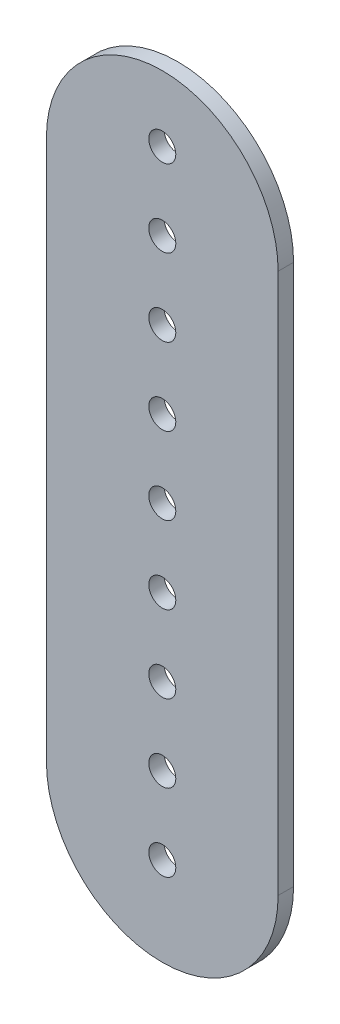
SolidWorks part; units mm, degrees
ref_plane "Front Plane" through (0, 0, 0) normal (0, 0, 1) x (1, 0, 0)
ref_plane "Top Plane" through (0, 0, 0) normal (0, 1, 0) x (1, 0, 0)
ref_plane "Right Plane" through (0, 0, 0) normal (1, 0, 0) x (0, 0, -1)
sketch "Sketch1" plane through (0, 0, 0) normal (0, 0, 1) x (1, 0, 0)
  line L0 (0, 0) -> (0, 70) construction
  line L1 (-15, 0) -> (-15, 70)
  line L2 (15, 0) -> (15, 70)
  arc A0 (-15, 0) -> (15, 0) centre (0, 0) ccw
  arc A1 (15, 70) -> (-15, 70) centre (0, 70) ccw
  point P3 (0, 35)
  dimension "D1" = 70
  dimension "D2" = 30
extrude "Boss-Extrude1" add sketch "Sketch1" along normal blind 2
sketch "Sketch2" plane through (0, 0, 2) normal (0, 0, 1) x (1, 0, 0)
  circle A0 centre (0, -3.5231) radius 1.75
  point P2 (0, -5.5366)
  point P3 (0, -3.5231)
  dimension "D1" = 3.5
extrude "Cut-Extrude1" cut sketch "Sketch2" against normal through all
pattern_linear "LPattern1" count 9 spacing 10 along (0, 1, 0) of "Cut-Extrude1"
